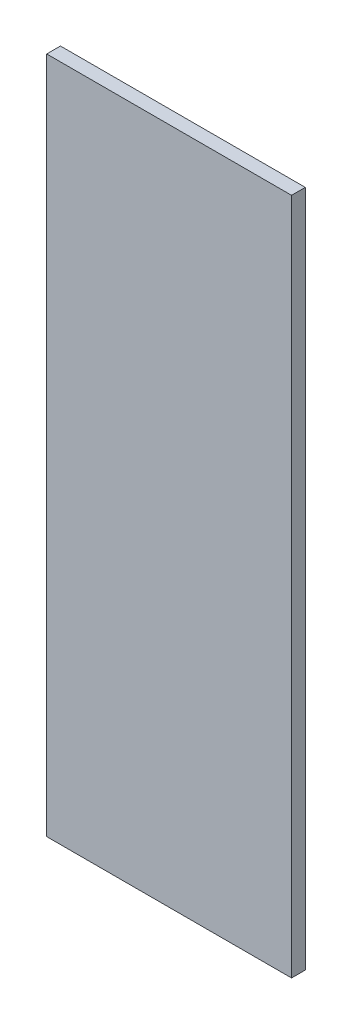
SolidWorks part; units mm, degrees
material "Custom Plastic"
ref_plane "X-Y Datum" through (0, 0, 0) normal (0, 0, 1) x (1, 0, 0)
ref_plane "X-Z Datum" through (0, 0, 0) normal (0, 1, 0) x (1, 0, 0)
ref_plane "Y-Z Datum" through (0, 0, 0) normal (1, 0, 0) x (0, 0, -1)
sketch "Sketch1" plane through (0, 0, 0) normal (0, 0, 1) x (1, 0, 0)
  line L1 (-28.275, 78.275) -> (28.275, 78.275)
  line L2 (-28.275, 78.275) -> (-28.275, -78.275)
  line L3 (-28.275, -78.275) -> (28.275, -78.275)
  line L4 (28.275, 78.275) -> (28.275, -78.275)
  line L5 (-28.275, 78.275) -> (28.275, -78.275) construction
  line L6 (-28.275, -78.275) -> (28.275, 78.275) construction
  point P0 (0, 0)
  dimension "D1" = 56.55
  dimension "D2" = 156.55
extrude "Boss-Extrude1" add sketch "Sketch1" along normal blind 3.175
